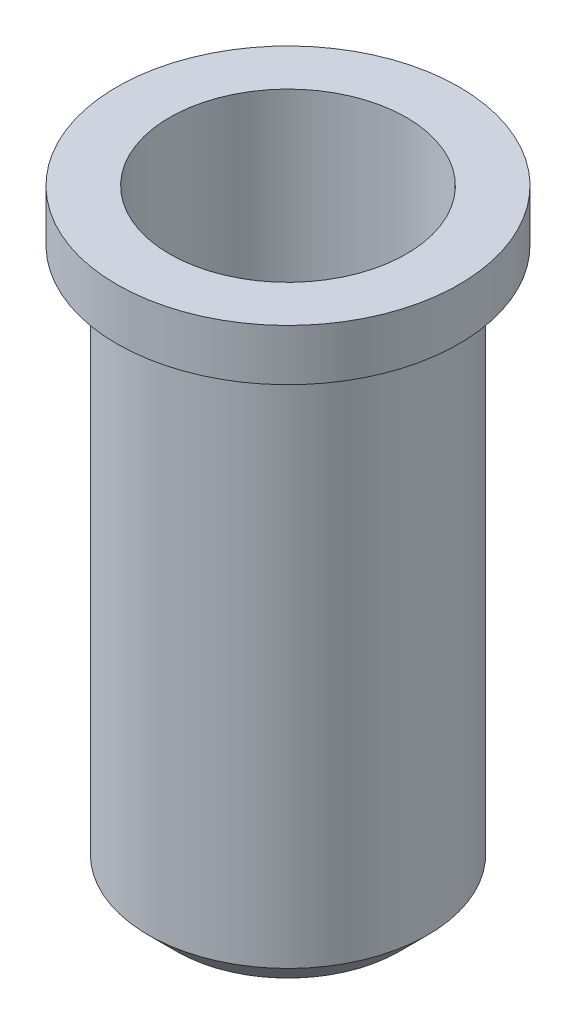
SolidWorks part; units mm, degrees
ref_plane "Front Plane" through (0, 0, 0) normal (0, 0, 1) x (1, 0, 0)
ref_plane "Top Plane" through (0, 0, 0) normal (0, 1, 0) x (1, 0, 0)
ref_plane "Right Plane" through (0, 0, 0) normal (1, 0, 0) x (0, 0, -1)
sketch "Sketch1" plane through (0, 0, 0) normal (0, 0, 1) x (1, 0, 0)
  line L0 (0, 0) -> (0, 8.4047) construction
  line L1 (0, 0) -> (0.9906, 0)
  line L2 (0, 0) -> (0, 0.254)
  line L4 (1.2446, 0.254) -> (1.2446, 4.953)
  line L8 (1.0541, 5.4102) -> (1.0541, 0.8382)
  line L9 (1.0541, 5.4102) -> (1.524, 5.4102)
  line L10 (1.0541, 5.4102) -> (1.0541, 7.9798)
  line L11 (1.2446, 4.953) -> (1.524, 4.953)
  line L12 (1.524, 5.4102) -> (1.524, 4.953)
  line L13 (1.2446, 0.254) -> (0.9906, 0)
  line L14 (1.0541, 0.8382) -> (0, 0.254)
  dimension "D1" = 0.4572
  dimension "D2" = 1.524
  dimension "D3" = 5.4102
  dimension "D4" = 1.2446
  dimension "D5" = 0.254
  dimension "D6" = 0.254
  dimension "D7" = 4.572
  dimension "D8" = 0.1905
  dimension "D9" = 0.254
revolve "Revolve1" add sketch "Sketch1" angle 360 about L0 region at (0.0562, 0.127, 0) other way angle 360
